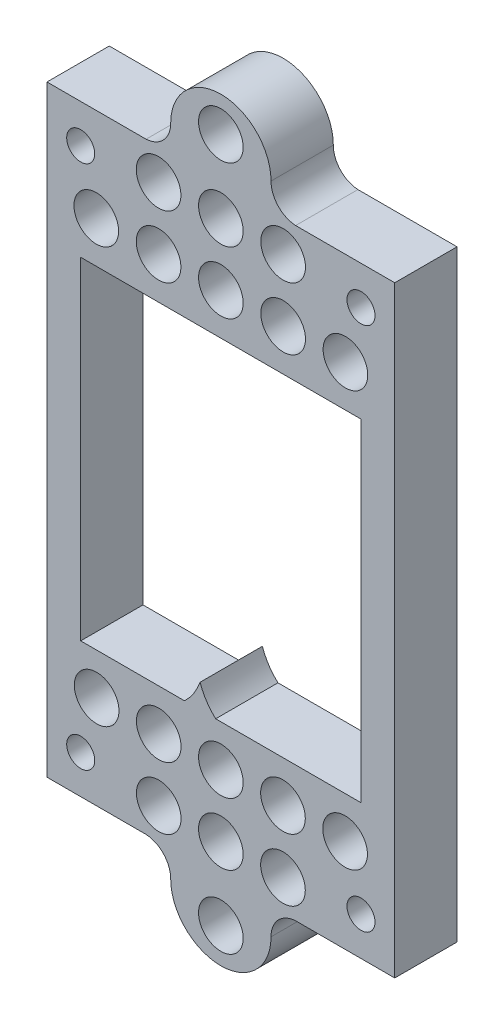
SolidWorks part; units mm, degrees
ref_plane "Front Plane" through (0, 0, 0) normal (0, 0, 1) x (1, 0, 0)
ref_plane "Top Plane" through (0, 0, 0) normal (0, 1, 0) x (1, 0, 0)
ref_plane "Right Plane" through (0, 0, 0) normal (1, 0, 0) x (0, 0, -1)
sketch "Sketch1" plane through (0, 0, 0) normal (0, 0, 1) x (1, 0, 0)
  line L0 (-13.5, -9.4654) -> (-2, -9.4654) construction
  line L1 (-16.75, 29) -> (-7.2028, 29)
  line L2 (-16.75, 29) -> (-16.75, -29)
  line L3 (-16.75, -29) -> (-7.2028, -29)
  line L4 (16.75, 29) -> (16.75, -29)
  line L5 (-13.5, 16) -> (13.5, 16)
  line L6 (-13.5, 16) -> (-13.5, -16)
  line L7 (-13.5, -16) -> (-3.5, -16)
  line L8 (13.5, 16) -> (13.5, -16)
  line L9 (-1.397, -14.9459) -> (-2.6159, -14.9374) construction
  line L10 (-1.15, -15.7286) -> (-2.85, -15.7286) construction
  line L11 (-2, -16) -> (-2, -13.7) construction
  line L12 (-0.5, -16) -> (13.5, -16)
  line L13 (-3.5, -16) -> (-0.5, -16) construction
  line L14 (-19.5, 29.3) -> (19.5, 29.3) construction
  line L15 (-19.5, 29.3) -> (-19.5, -29.3) construction
  line L16 (-19.5, -29.3) -> (19.5, -29.3) construction
  line L17 (19.5, 29.3) -> (19.5, -29.3) construction
  line L18 (-4, 30) -> (4, 30) construction
  line L19 (-5, 27.5542) -> (5, 27.5542) construction
  line L20 (0, 0) -> (4.3335, 0) construction
  line L21 (7.2028, 29) -> (16.75, 29)
  line L22 (7.2028, -29) -> (16.75, -29)
  line L23 (0, 33) -> (0, 28.0589) construction
  arc A0 (-3.5, -16) -> (-2, -13.7) centre (-7.6154, -11.6769) ccw
  arc A1 (-0.5, -16) -> (-2, -13.7) centre (3.1751, -11.9641) cw
  circle A2 centre (-13.5, 25.3) radius 1.35
  circle A4 centre (13.5, -25.3) radius 1.35
  circle A5 centre (-13.5, -25.3) radius 1.35
  circle A6 centre (13.5, 25.3) radius 1.35
  arc A7 (-4.8326, 31.5247) -> (4.8326, 31.5247) centre (0, 31.5247) cw
  circle A8 centre (0, 33) radius 2.15
  circle A13 centre (0, -33) radius 2.15
  arc A16 (-4.8326, 31.5247) -> (-7.2028, 29) centre (-7.3434, 31.5069) cw
  arc A17 (4.8326, 31.5247) -> (7.2028, 29) centre (7.3434, 31.5069) ccw
  arc A21 (4.8326, -31.5247) -> (7.2028, -29) centre (7.3434, -31.5069) cw
  arc A22 (-4.8326, -31.5247) -> (-7.2028, -29) centre (-7.3434, -31.5069) ccw
  arc A23 (-4.8326, -31.5247) -> (4.8326, -31.5247) centre (0, -31.5247) ccw
  point P10 (-16.75, 0)
  point P11 (0, 16)
  point P12 (-13.5, 0)
  point P21 (-2, -15.7286)
  point P29 (19.5, 0)
  point P30 (0, 29.3)
  point P37 (-2, -16)
  point P39 (0, 30)
  point P46 (0, 27.5542)
  dimension "D8" = 2.7
  dimension "D22" = 4.3
  dimension "D23" = 4
  dimension "D1" = 27
  dimension "D2" = 33.5
  dimension "D3" = 58
  dimension "D4" = 32
  dimension "D5" = 11.5
  dimension "D6" = 3
  dimension "D7" = 2.3
  dimension "D9" = 58.6
  dimension "D10" = 39
  dimension "D11" = 6
  dimension "D12" = 4
  dimension "D13" = 4
  dimension "D14" = 6
  dimension "D15" = 6
  dimension "D16" = 6
  dimension "D17" = 4
  dimension "D18" = 4
  dimension "D19" = 8
  dimension "D20" = 1
  dimension "D21" = 10
extrude "Boss-Extrude1" add sketch "Sketch1" along normal blind 6
sketch "Sketch2" plane through (0, 0, 6) normal (0, 0, 1) x (1, 0, 0)
  line L2 (-13.5, -16) -> (-3.5, -16) construction
  line L3 (13.5, 16) -> (-13.5, 16) construction
  circle A0 centre (-12, 20) radius 2.15
  circle A1 centre (-6, 20) radius 2.15
  circle A2 centre (0, 20) radius 2.15
  circle A3 centre (6, 20) radius 2.15
  circle A4 centre (12, 20) radius 2.15
  circle A5 centre (-6, 26) radius 2.15
  circle A6 centre (0, 26) radius 2.15
  circle A7 centre (6, 26) radius 2.15
  circle A8 centre (-11.9673, -20) radius 2.15
  circle A9 centre (-5.9837, -20) radius 2.15
  circle A10 centre (0, -20) radius 2.15
  circle A11 centre (5.9837, -20) radius 2.15
  circle A12 centre (11.9673, -20) radius 2.15
  circle A13 centre (-5.9837, -26) radius 2.15
  circle A14 centre (0, -26) radius 2.15
  circle A15 centre (5.9837, -26) radius 2.15
  dimension "D1" = 4.3
  dimension "D5" = 4.3
  dimension "D11" = 4.3
  dimension "D12" = 4.3
  dimension "D13" = 4.3
  dimension "D14" = 4.3
  dimension "D15" = 4.3
  dimension "D16" = 4.3
  dimension "D2" = 4
  dimension "D3" = 4
  dimension "D6" = 6
  dimension "D10" = 6
  dimension "D4" = 5
  dimension "D9" = 5
extrude "Cut-Extrude1" cut sketch "Sketch2" against normal blind 4.2
